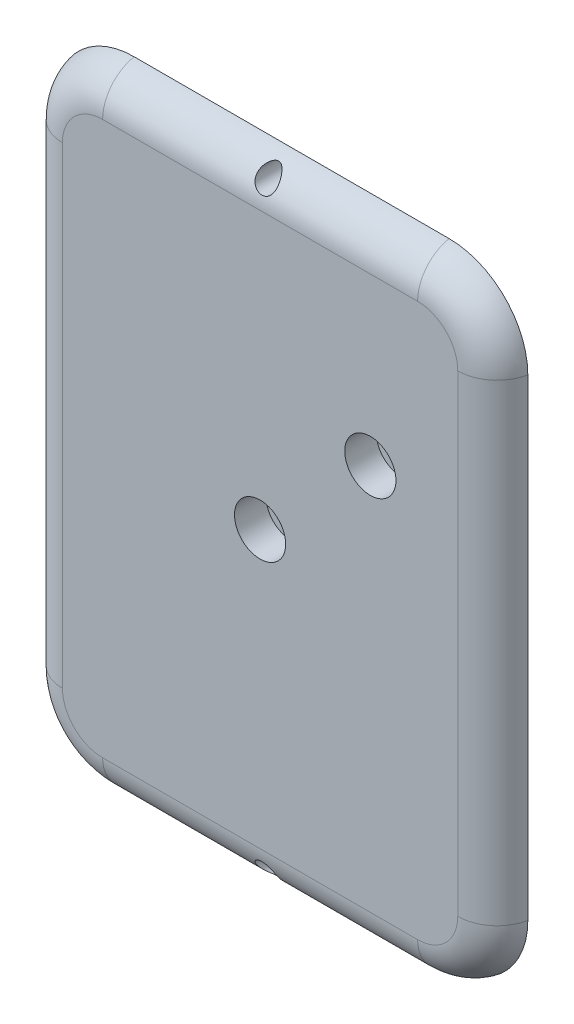
SolidWorks part; units mm, degrees
ref_plane "Front Plane" through (0, 0, 0) normal (0, 0, 1) x (1, 0, 0)
ref_plane "Top Plane" through (0, 0, 0) normal (0, 1, 0) x (1, 0, 0)
ref_plane "Right Plane" through (0, 0, 0) normal (1, 0, 0) x (0, 0, -1)
sketch "草圖1" plane through (0, 0, 0) normal (0, 0, 1) x (1, 0, 0)
  line L0 (25.7, -30) -> (25.7, 30)
  line L1 (20, 35.7) -> (-20, 35.7)
  line L2 (-25.7, 30) -> (-25.7, -30)
  line L3 (-20, -35.7) -> (20, -35.7)
  arc A0 (20, -35.7) -> (25.7, -30) centre (20, -30) ccw
  arc A1 (25.7, 30) -> (20, 35.7) centre (20, 30) ccw
  arc A2 (-20, 35.7) -> (-25.7, 30) centre (-20, 30) ccw
  arc A3 (-25.7, -30) -> (-20, -35.7) centre (-20, -30) ccw
extrude "填料-伸長1" add sketch "草圖1" along normal blind 3
sketch "草圖2" plane through (0, 0, 0) normal (0, 0, 1) x (1, 0, 0)
  line L0 (30, -30) -> (30, 30)
  line L1 (20, 40) -> (-20, 40)
  line L2 (-30, 30) -> (-30, -30)
  line L3 (-20, -40) -> (20, -40)
  arc A0 (20, -40) -> (30, -30) centre (20, -30) ccw
  arc A1 (30, 30) -> (20, 40) centre (20, 30) ccw
  arc A2 (-20, 40) -> (-30, 30) centre (-20, 30) ccw
  arc A3 (-30, -30) -> (-20, -40) centre (-20, -30) ccw
  circle A4 centre (0, 38) radius 1.35
  circle A5 centre (0, -38) radius 1.35
  circle A6 centre (0, 0) radius 3.25
  circle A7 centre (14, 14) radius 3.25
extrude "填料-伸長2" add sketch "草圖2" along normal blind 4 from offset 3
fillet "圓角1" radius 5 8 edges at (27.0711, -37.0711, 7) (30, 0, 7) (27.0711, 37.0711, 7) (0, 40, 7) (-27.0711, 37.0711, 7) (-30, 0, 7) (-27.0711, -37.0711, 7) (0, -40, 7)
